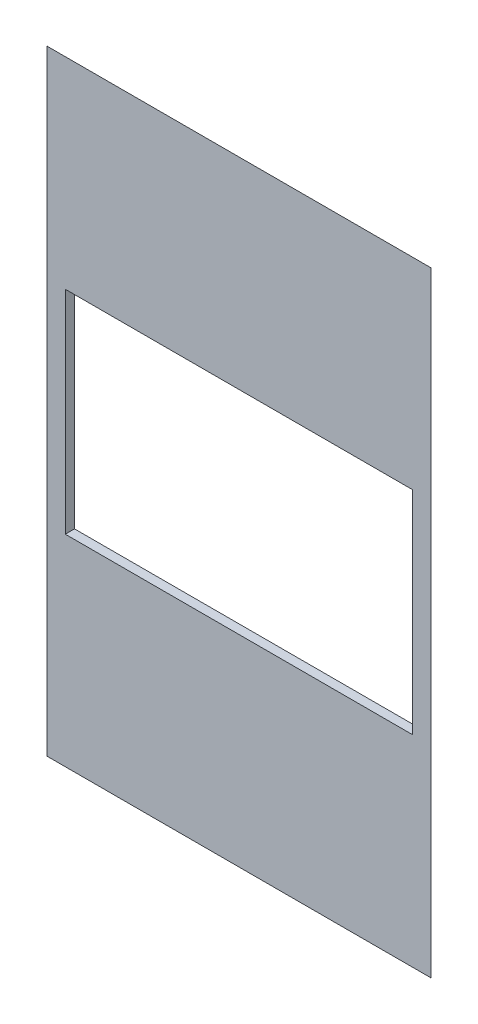
SolidWorks part; units mm, degrees
other "Markup1"
sketch "Sketch4" plane through (0, 750, 0) normal (-0.3936, 0.2648, -0.8803) x (-0.8349, 0.2978, 0.4628)
ref_plane "Front Plane" through (0, 0, 0) normal (0, 0, 1) x (1, 0, 0)
ref_plane "Top Plane" through (0, 0, 0) normal (0, 1, 0) x (1, 0, 0)
ref_plane "Right Plane" through (0, 0, 0) normal (1, 0, 0) x (0, 0, -1)
sketch "Sketch1" plane through (0, 0, 0) normal (0, 0, 1) x (1, 0, 0)
  line L1 (0, 0) -> (500, 0)
  line L2 (0, 0) -> (0, 800)
  line L3 (0, 800) -> (500, 800)
  line L4 (500, 0) -> (500, 800)
  line L5 (12, 12) -> (488, 12)
  line L6 (12, 12) -> (12, 788)
  line L7 (12, 788) -> (488, 788)
  line L8 (488, 12) -> (488, 788)
  line L9 (12, 250) -> (488, 250)
  line L10 (12, 250) -> (12, 550)
  line L11 (12, 550) -> (488, 550)
  line L12 (488, 250) -> (488, 550)
  line L13 (24, 538) -> (476, 538)
  line L14 (24, 538) -> (24, 262)
  line L15 (24, 262) -> (476, 262)
  line L16 (476, 538) -> (476, 262)
  dimension "D1" = 500
  dimension "D2" = 800
  dimension "D3" = 12
  dimension "D4" = 12
  dimension "D5" = 12
  dimension "D6" = 12
  dimension "D7" = 300
  dimension "D8" = 250
  dimension "D9" = 250
  dimension "D10" = 12
  dimension "D11" = 12
  dimension "D12" = 12
  dimension "D13" = 12
extrude "Boss-Extrude1" add sketch "Sketch1" along normal blind 12 contours L2 L1 L4 L3
extrude "Cut-Extrude1" cut sketch "Sketch1<5>" along normal through all contours L16 L13 L14 L15 region at (250, 400, 0)
sketch "Sketch1<5>" plane through (0, 0, 0) normal (0, 0, 1) x (1, 0, 0) same geometry as "Sketch1"
chamfer "Chamfer1" distance 12 4 edges at (250, 0, 0) (0, 400, 0) (250, 800, 0) (500, 400, 0)
